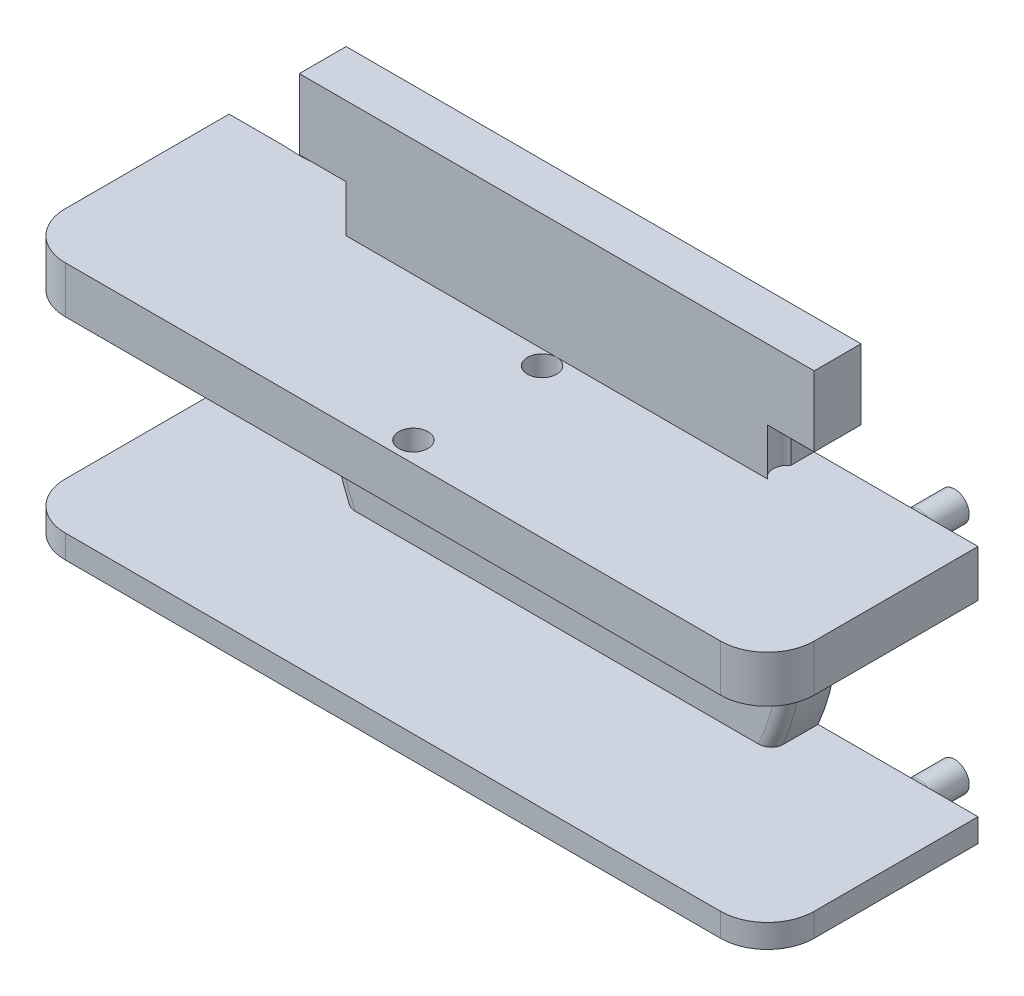
SolidWorks part; units mm, degrees
material "UNOBTANIUM"
ref_plane "Top Plane" through (0, 0, 0) normal (0, 0, 1) x (1, 0, 0)
ref_plane "Right Plane" through (0, 0, 0) normal (0, 1, 0) x (1, 0, 0)
ref_plane "Front Plane" through (0, 0, 0) normal (1, 0, 0) x (0, 0, -1)
ref_axis "x-axis" through (-17.6, 0, 0) along (1, 0, 0)
ref_axis "y-axis" through (0, -9.7375, 0) along (0, 1, 0)
ref_axis "z-axis" through (0, 0, 8.775) along (0, 0, -1)
sketch "Sketch1" plane through (0, 0, 0) normal (0, 0, 1) x (1, 0, 0)
  line L0 (-11, 6) -> (-11, 11)
  line L1 (-11, -6) -> (11, -6)
  line L2 (-11, -6) -> (-11, 6)
  line L3 (-11, 6) -> (11, 6) construction
  line L4 (11, -6) -> (11, 6)
  line L5 (-11, -6) -> (11, 6) construction
  line L6 (-11, 6) -> (11, -6) construction
  line L7 (-11, 11) -> (11, 11)
  line L8 (11, 11) -> (11, 6)
  circle A0 centre (0, 0) radius 9.25 construction
  point P0 (0, 0)
  dimension "D1" = 18.5
  dimension "D2" = 22
  dimension "D3" = 12
  dimension "D4" = 5
extrude "Boss-Extrude1" add sketch "Sketch1" along normal blind 2
sketch "Sketch2" plane through (0, 0, 2) normal (0, 0, -1) x (-1, 0, 0)
  circle A0 centre (0, 0) radius 1.54
  dimension "D1" = 3.08
extrude "Boss-Extrude2" add sketch "Sketch2" along normal blind 4 separate body
sketch "Sketch3" plane through (0, 0, 0) normal (0, 0, -1) x (-1, 0, 0)
  line L0 (11, -6) -> (-11, 6) construction
  circle A0 centre (0, 0) radius 3.5
  dimension "D1" = 7
extrude "Boss-Extrude3" add sketch "Sketch3" along normal blind 1
sketch "Sketch4" plane through (0, 0, 0) normal (0, 0, -1) x (-1, 0, 0)
  line L0 (11, -6) -> (-11, -6) construction
  line L1 (11, 11) -> (9, 11)
  line L2 (11, 11) -> (11, -6)
  line L3 (11, -6) -> (9, -6)
  line L4 (9, 11) -> (9, -6)
  line L5 (0, -6) -> (0, 11) construction
  line L7 (-9, 11) -> (-9, -6)
  line L8 (-11, -6) -> (-9, -6)
  line L9 (-11, 11) -> (-11, -6)
  line L10 (-11, 11) -> (-9, 11)
  line L11 (11, 11) -> (-11, 11) construction
  dimension "D1" = 2
extrude "Boss-Extrude4" add sketch "Sketch4" along normal blind 0.001
sketch "Sketch5" plane through (0, 0, 0) normal (0, 0, -1) x (-1, 0, 0)
  line L0 (-9, -6) -> (-9, 11) construction
  line L1 (9, 11) -> (-9, 11)
  line L2 (9, 11) -> (9, 9)
  line L3 (9, 9) -> (-9, 9)
  line L4 (-9, 11) -> (-9, 9)
  dimension "D1" = 2
extrude "Boss-Extrude5" add sketch "Sketch5" along normal up to surface (0.001 mm away) up to face at (-10, 2.5, -0.001)
sketch "Sketch6" plane through (11, 0, 0) normal (1, 0, 0) x (0, 0, -1)
  line L0 (-2, -6) -> (-2, 11) construction
  line L1 (0.001, -6) -> (-2, -6)
  line L2 (0.001, -6) -> (0.001, -4)
  line L3 (0.001, -4) -> (-2, -4)
  line L4 (-2, -6) -> (-2, -4)
  line L6 (0.001, 11) -> (0.001, -6) construction
  line L7 (-2, 6) -> (0.001, 6)
  line L8 (-2, 6) -> (-2, 4)
  line L9 (-2, 4) -> (0.001, 4)
  line L10 (0.001, 6) -> (0.001, 4)
  dimension "D1" = 2
extrude "Boss-Extrude6" add sketch "Sketch6" along normal blind 5
mirror "Mirror1" about plane through (0, 0, 0) normal (1, 0, 0) of "Boss-Extrude6"
sketch "Sketch7" plane through (0, 0, -0.001) normal (0, 0, -1) x (-1, 0, 0)
  line L0 (-9, -6) -> (-9, 9) construction
  line L1 (-9, 0) -> (-9, 9)
  line L2 (-9, 9) -> (0, 9)
  line L3 (-9, 0) -> (-9, -6)
  line L4 (-9, -6) -> (-6.7082, -6)
  line L5 (11, -6) -> (-11, -6) construction
  arc A0 (0, 9) -> (-6.7082, -6) centre (0, 0) ccw
  line M18 (-9, -6) -> (-9, 9)
  line M19 (-9, 9) -> (9, 9)
extrude "Boss-Extrude7" add sketch "Sketch7" against normal up to surface (0.001 mm away) contours A0 L4 M18 | A0 M19 M18 region at (8.3306, -4.5409, -0.001) region at (6.9897, 6.9897, -0.001) up to face at (3.5, 0, 0)
sketch "Sketch8" plane through (0, 0, -0.001) normal (0, 0, -1) x (-1, 0, 0)
  line L0 (-11, 4) -> (-9.1652, 4)
  line L1 (-11, 4) -> (-11, -4)
  line L2 (-11, -4) -> (-9.1652, -4)
  arc A1 (-9.1652, 4) -> (-9.1652, -4) centre (0, 0) ccw
  dimension "D1" = 10
extrude "Cut-Extrude1" cut sketch "Sketch8" against normal through all
sketch "Sketch9" plane through (0, 0, -0.001) normal (0, 0, -1) x (-1, 0, 0)
  line L0 (-16, -4) -> (-9.1652, -4) construction
  line L1 (-8.0623, 4) -> (-11, 4)
  line L2 (-8.0623, 4) -> (-8.0623, -4)
  line L3 (-8.0623, -4) -> (-11, -4)
  line L4 (-11, 4) -> (-11, -4)
  line L5 (-11, -6) -> (-11, 6) construction
  arc A0 (0, 9) -> (-6.7082, -6) centre (0, 0) ccw construction
  arc A1 (0, 9) -> (-6.7082, -6) centre (0, 0) ccw construction
extrude "Cut-Extrude2" cut sketch "Sketch9" against normal up to surface (0.001 mm away) up to face at (3.5, 0, 0)
mirror "Mirror2" about plane through (0, 0, 0) normal (1, 0, 0) of "Cut-Extrude2", "Boss-Extrude7", "Cut-Extrude1"
sketch "Sketch21" plane through (0, 0, -0.001) normal (0, 0, -1) x (-1, 0, 0)
  circle A0 centre (0, 0) radius 9.75
  circle A1 centre (0, 0) radius 9 construction
  circle A2 centre (0, 0) radius 3.5 construction
  circle A3 centre (0, 0) radius 3.5
  dimension "D1" = 0.75
extrude "Cut-Extrude11" cut sketch "Sketch21" against normal up to surface (0.001 mm away) up to face at (0, -0.7091, 0)
sketch "Sketch10" plane through (0, 0, 2) normal (0, 0, 1) x (1, 0, 0)
  line L0 (-16, -4) -> (-16, -6) construction
  line L1 (16, -6) -> (-16, -6)
  line L2 (16, -6) -> (16, -4)
  line L3 (16, -4) -> (-16, -4)
  line L4 (-16, -6) -> (-16, -4)
  line L5 (-16, -4) -> (-9.1652, -4) construction
  line L7 (-16, 6) -> (16, 6)
  line L8 (-16, 6) -> (-16, 4)
  line L9 (-16, 4) -> (16, 4)
  line L10 (16, 6) -> (16, 4)
extrude "Boss-Extrude8" add sketch "Sketch10" along normal blind 7
fillet "Fillet1" radius 0.5 2 edges at (10, 0, 2) (-10, 0, 2)
sketch "Sketch11" plane through (0, 0, -0.001) normal (0, 0, -1) x (-1, 0, 0)
  line L0 (-16, -5) -> (-13, -5) construction
  line L1 (-16, -6) -> (-16, -4) construction
  circle A0 centre (-13, -5) radius 0.625
  dimension "D1" = 1.25
  dimension "D2" = 3
extrude "Boss-Extrude9" add sketch "Sketch11" along normal blind 2
sketch "Sketch14" plane through (0, 0, -0.001) normal (0, 0, -1) x (-1, 0, 0)
  line L1 (11, 6) -> (9, 6)
  line L2 (11, 6) -> (11, 8)
  line L3 (11, 8) -> (9, 8)
  line L4 (9, 6) -> (9, 8)
  line L5 (-11, 6) -> (-9, 6)
  line L6 (-11, 6) -> (-11, 8)
  line L7 (-11, 8) -> (-9, 8)
  line L8 (-9, 6) -> (-9, 8)
  dimension "D1" = 18
  dimension "D2" = 2
extrude "Cut-Extrude5" cut sketch "Sketch14" against normal through all
sketch "Sketch12" plane through (0, 0, -0.001) normal (0, 0, -1) x (-1, 0, 0)
  line L0 (-16, -5) -> (-13, -5) construction
  line L1 (-16, -6) -> (-16, -4) construction
  line L3 (16, -5) -> (13, -5) construction
  line L4 (16, -6) -> (16, -4) construction
  circle A0 centre (13, -5) radius 0.675
  circle A1 centre (-13, -5) radius 0.625 construction
  circle A2 centre (-13, -5) radius 0.625 construction
  dimension "D1" = 1.35
  dimension "D2" = 1.25
extrude "Cut-Extrude3" cut sketch "Sketch12" against normal blind 2.5
sketch "Sketch16" plane through (0, 6, 0) normal (0, 1, 0) x (1, 0, 0)
  line L0 (-9, -2) -> (-9, 0.001) construction
  line L1 (-9, -1) -> (-9, -2)
  arc A1 (-9, -1) -> (-9, -2) centre (-9.375, -1.5) cw
  dimension "D1" = 0.25
  dimension "D2" = 1
extrude "Cut-Extrude6" cut sketch "Sketch16" along normal blind 2
mirror "Mirror3" about plane through (0, 0, 0) normal (0, 1, 0) of "Boss-Extrude9", "Cut-Extrude3"
mirror "Mirror4" about plane through (0, 0, 0) normal (1, 0, 0) of "Cut-Extrude6"
fillet "Fillet2" radius 0.5 2 edges at (12.375, 5, -0.001) (13.625, -5, -0.001)
fillet "Fillet3" radius 0.5 2 edges at (-13.675, 5, -0.001) (-13.675, -5, -0.001)
fillet "Fillet4" radius 2 4 edges at (16, -5, 9) (16, 5, 9) (-16, -5, 9) (-16, 5, 9)
sketch "Sketch17" plane through (0, -6, 0) normal (0, -1, 0) x (1, 0, 0)
  line L0 (-16, 7) -> (-16, -0.001) construction
  line L1 (-14, 9) -> (14, 9) construction
  line L2 (16, 7) -> (16, -0.001) construction
  line L3 (-16, 7) -> (-16, -0.001)
  line L4 (-14, 9) -> (14, 9)
  line L5 (16, 7) -> (16, -0.001)
  line L6 (14.5, 7) -> (14.5, -0.001)
  line L8 (-14, 7.5) -> (14, 7.5)
  line L9 (-14.5, 7) -> (-14.5, -0.001)
  line L10 (14.5, -0.001) -> (16, -0.001)
  line L11 (-14.5, -0.001) -> (-16, -0.001)
  arc A0 (-14, 9) -> (-16, 7) centre (-14, 7) ccw construction
  arc A1 (16, 7) -> (14, 9) centre (14, 7) ccw construction
  arc A2 (-14, 9) -> (-16, 7) centre (-14, 7) ccw
  arc A3 (16, 7) -> (14, 9) centre (14, 7) ccw
  arc A4 (14.5, 7) -> (14, 7.5) centre (14, 7) ccw
  arc A5 (-14, 7.5) -> (-14.5, 7) centre (-14, 7) ccw
  dimension "D1" = 1.5
extrude "Cut-Extrude7" cut sketch "Sketch17" against normal blind 1 and the other way through all
sketch "Sketch19" plane through (0, 6, 0) normal (0, 1, 0) x (1, 0, 0)
  line L0 (9, -2) -> (-9, -2) construction
  line L1 (0, -2.625) -> (0, -2) construction
  line L2 (9, -2) -> (-9, -2) construction
  circle A0 centre (0, -2.625) radius 0.625
  circle A1 centre (0, -8.125) radius 0.625
  point P4 (0, -2)
  dimension "D1" = 1.25
  dimension "D2" = 5.5
extrude "Cut-Extrude9" cut sketch "Sketch19" against normal up to surface (2 mm away) up to face at (0.0154, 4, 1.9997)
sketch "Sketch20" plane through (0, 0, -0.001) normal (0, 0, -1) x (-1, 0, 0)
  line L0 (-9, 8) -> (-11, 8) construction
  line L1 (-11, 11) -> (-9, 11)
  line L2 (-11, 11) -> (-11, 8)
  line L3 (-11, 8) -> (-9, 8)
  line L4 (-9, 11) -> (-9, 8)
  line L5 (11, 11) -> (-11, 11) construction
  line L6 (11, 8) -> (9, 8)
  line L7 (11, 8) -> (11, 11)
  line L8 (11, 11) -> (9, 11)
  line L9 (9, 8) -> (9, 11)
  dimension "D1" = 2
combine bodies "Combine2" operation type subtract main body 122 bodies to subtract 102
equation "\"D1@Sketch12\"=\"D2@Sketch12\"+.1"
